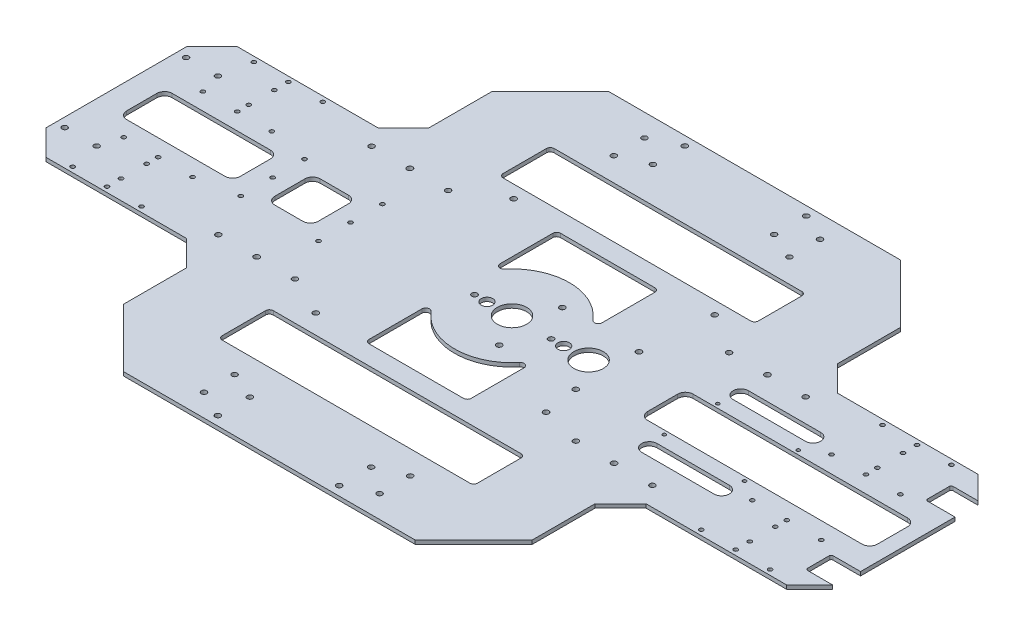
SolidWorks part; units mm, degrees
material "6061-O (SS)"
ref_plane "前视基准面" through (0, 0, 0) normal (0, 0, 1) x (1, 0, 0)
ref_plane "上视基准面" through (0, 0, 0) normal (0, 1, 0) x (1, 0, 0)
ref_plane "右视基准面" through (0, 0, 0) normal (1, 0, 0) x (0, 0, -1)
sketch "草图1" plane through (0, 0, 0) normal (0, 1, 0) x (1, 0, 0)
  line L0 (-310, 75) -> (310, -75) construction
  line L1 (-260, 200) -> (260, 200) construction
  line L2 (-260, 200) -> (-260, -200) construction
  line L3 (-260, -200) -> (260, -200) construction
  line L4 (260, 200) -> (260, -200) construction
  line L5 (310, 75) -> (-310, -75) construction
  line L6 (-160, 200) -> (160, -200) construction
  line L7 (-310, -75) -> (-160, -75)
  line L8 (-310, -75) -> (-310, 75)
  line L9 (-310, 75) -> (-160, 75)
  line L10 (310, -75) -> (310, 75)
  line L11 (160, 200) -> (-160, -200) construction
  line L13 (-160, -200) -> (160, -200)
  line L14 (-160, -200) -> (-160, -75)
  line L15 (-160, 200) -> (160, 200)
  line L16 (160, -200) -> (160, -75)
  line L19 (-160, 75) -> (-160, 200)
  line L22 (160, 75) -> (310, 75)
  line L25 (160, 75) -> (160, 200)
  line L28 (160, -75) -> (310, -75)
  point P0 (0, 0)
  point P6 (-0.5159, 0.1248)
  point P11 (0, 0)
  dimension "D1" = 520
  dimension "D2" = 400
  dimension "D3" = 50
  dimension "D4" = 125
  dimension "D5" = 100
extrude "凸台-拉伸1" add sketch "草图1" along normal blind 3
chamfer "倒角1" distance 20 angle 45 8 edges at (-160, 1.5, -75) (-310, 1.5, -75) (-310, 1.5, 75) (-160, 1.5, 75) (160, 1.5, 75) (160, 1.5, -75) (310, 1.5, 75) (310, 1.5, -75)
sketch "草图2" plane through (0, 3, 0) normal (0, 1, 0) x (1, 0, 0)
  line L0 (-160, 200) -> (-160, 95) construction
  line L1 (-160, 180) -> (160, 180)
  line L2 (-160, 180) -> (-160, 200)
  line L3 (-160, 200) -> (160, 200)
  line L4 (160, 180) -> (160, 200)
  line L6 (160, -200) -> (-160, -200)
  line L7 (160, -200) -> (160, -180)
  line L8 (160, -180) -> (-160, -180)
  line L9 (-160, -200) -> (-160, -180)
  dimension "D1" = 20
  dimension "D2" = 20
extrude "切除-拉伸1" cut sketch "草图2" against normal blind 5
chamfer "倒角2" distance 50 angle 45 4 edges at (-160, 1.5, -180) (-160, 1.5, 180) (160, 1.5, -180) (160, 1.5, 180)
sketch "草图3" plane through (0, 3, 0) normal (0, 1, 0) x (1, 0, 0)
  line L0 (0, 0) -> (144.0598, 0) construction
  line L1 (110, -180) -> (-110, -180) construction
  circle A0 centre (-302.8263, 47.5) radius 2.1
  circle A1 centre (-277.8263, 47.5) radius 2.1
  circle A2 centre (-47.5, 182.8263) radius 2.1
  circle A3 centre (-47.5, 157.8263) radius 2.1
  circle A4 centre (47.5, 182.8263) radius 2.1
  circle A5 centre (47.5, 157.8263) radius 2.1
  circle A6 centre (302.7002, 47.5) radius 2.1
  circle A7 centre (327.7002, 47.5) radius 2.1
  circle A8 centre (-68.75, 172.5) radius 2.1
  circle A9 centre (-68.75, 148.5) radius 2.1
  circle A10 centre (68.75, 172.5) radius 2.1
  circle A11 centre (68.75, 148.5) radius 2.1
  circle A12 centre (68.75, -148.5) radius 2.1
  circle A13 centre (68.75, -172.5) radius 2.1
  circle A14 centre (-68.75, -148.5) radius 2.1
  circle A15 centre (-68.75, -172.5) radius 2.1
  circle A16 centre (327.7002, -47.5) radius 2.1
  circle A17 centre (302.7002, -47.5) radius 2.1
  circle A18 centre (47.5, -157.8263) radius 2.1
  circle A19 centre (47.5, -182.8263) radius 2.1
  circle A20 centre (-47.5, -157.8263) radius 2.1
  circle A21 centre (-47.5, -182.8263) radius 2.1
  circle A22 centre (-277.8263, -47.5) radius 2.1
  circle A23 centre (-302.8263, -47.5) radius 2.1
  dimension "D1" = 4.2
  dimension "D2" = 4.2
  dimension "D3" = 4.2
  dimension "D4" = 4.2
  dimension "D5" = 4.2
  dimension "D6" = 4.2
  dimension "D7" = 4.2
  dimension "D8" = 4.2
  dimension "D9" = 180
extrude "切除-拉伸2" cut sketch "草图3" against normal blind 80
sketch "草图4" plane through (0, 0, 0) normal (0, -1, 0) x (1, 0, 0)
  circle A0 centre (-78.74, 74.91) radius 2.15
  arc A1 (-76.765, 74.91) -> (-80.715, 74.91) centre (-78.74, 74.91) ccw construction
  circle A2 centre (-78.74, -80.01) radius 2.15
  circle A3 centre (78.74, -80.01) radius 2.15
  circle A4 centre (78.74, 52.07) radius 2.15
  dimension "D1" = 4.3
  dimension "D2" = 4.3
  dimension "D3" = 4.3
  dimension "D4" = 4.3
extrude "切除-拉伸3" cut sketch "草图4" against normal blind 10
sketch "草图5" plane through (0, 3, 0) normal (0, 1, 0) x (1, 0, 0)
  line L0 (0, 0) -> (90.3311, 0) construction
  line L1 (0, 0) -> (0, 46.0052) construction
  circle A0 centre (219.2002, 71) radius 1.6
  circle A1 centre (273.2002, 71) radius 1.6
  circle A2 centre (246.2002, 71) radius 1.6
  circle A3 centre (219.2002, 30.9984) radius 1.6
  circle A4 centre (246.2002, 30.9984) radius 1.6
  circle A5 centre (273.2002, 30.9984) radius 1.6
  circle A6 centre (246.2002, 60) radius 1.6
  circle A7 centre (246.2002, 40) radius 1.6
  circle A8 centre (246.2002, -40) radius 1.6
  circle A9 centre (246.2002, -60) radius 1.6
  circle A10 centre (273.2002, -30.9984) radius 1.6
  circle A11 centre (246.2002, -30.9984) radius 1.6
  circle A12 centre (219.2002, -30.9984) radius 1.6
  circle A13 centre (246.2002, -71) radius 1.6
  circle A14 centre (273.2002, -71) radius 1.6
  circle A15 centre (219.2002, -71) radius 1.6
  circle A16 centre (-219.2002, -71) radius 1.6
  circle A17 centre (-273.2002, -71) radius 1.6
  circle A18 centre (-246.2002, -71) radius 1.6
  circle A19 centre (-219.2002, -30.9984) radius 1.6
  circle A20 centre (-246.2002, -30.9984) radius 1.6
  circle A21 centre (-273.2002, -30.9984) radius 1.6
  circle A22 centre (-246.2002, -60) radius 1.6
  circle A23 centre (-246.2002, -40) radius 1.6
  circle A24 centre (-246.2002, 40) radius 1.6
  circle A25 centre (-246.2002, 60) radius 1.6
  circle A26 centre (-273.2002, 30.9984) radius 1.6
  circle A27 centre (-246.2002, 30.9984) radius 1.6
  circle A28 centre (-219.2002, 30.9984) radius 1.6
  circle A29 centre (-246.2002, 71) radius 1.6
  circle A30 centre (-273.2002, 71) radius 1.6
  circle A31 centre (-219.2002, 71) radius 1.6
  circle A32 centre (170, -60) radius 2.1
  circle A34 centre (110, -60) radius 2.1
  circle A35 centre (140, -60) radius 2.2
  circle A36 centre (140, 60) radius 2.2
  circle A37 centre (110, 60) radius 2.1
  circle A38 centre (170, 60) radius 2.1
  circle A39 centre (-170, 60) radius 2.1
  circle A40 centre (-110, 60) radius 2.1
  circle A41 centre (-140, 60) radius 2.2
  circle A42 centre (-140, -60) radius 2.2
  circle A43 centre (-110, -60) radius 2.1
  circle A44 centre (-170, -60) radius 2.1
  dimension "D1" = 3.2
extrude "切除-拉伸4" cut sketch "草图5" against normal blind 29
sketch "草图6" plane through (0, 3, 0) normal (0, 1, 0) x (1, 0, 0)
  line L0 (160, -150) -> (160, -95) construction
  line L1 (0, 0) -> (166.252, 0) construction
  line L2 (-160, 130) -> (-110, 180)
  line L3 (110, 180) -> (-110, 180)
  line L4 (110, 180) -> (160, 130)
  line L5 (-160, -95) -> (-160, -150) construction
  line L12 (160, -144.1421) -> (160, -130)
  line L13 (114.1421, -190) -> (160, -144.1421)
  line L14 (52.4797, -190) -> (114.1421, -190)
  line L15 (-114.1421, -190) -> (-52, -190)
  line L16 (-160, -144.1421) -> (-114.1421, -190)
  line L17 (-160, -130) -> (-160, -144.1421)
  line L25 (-52, -190) -> (52.4797, -190)
  line L28 (110, -180) -> (160, -130) construction
  line L29 (110, -180) -> (-110, -180) construction
  line L30 (-160, -130) -> (-110, -180) construction
  line L31 (110, -180) -> (160, -130)
  line L32 (110, -180) -> (-110, -180)
  line L33 (-160, -130) -> (-110, -180)
  line L37 (-52, 190) -> (52.4797, 190)
  line L38 (-160, 130) -> (-160, 144.1421)
  line L39 (-160, 144.1421) -> (-114.1421, 190)
  line L40 (-114.1421, 190) -> (-52, 190)
  line L41 (52.4797, 190) -> (114.1421, 190)
  line L42 (114.1421, 190) -> (160, 144.1421)
  line L43 (160, 144.1421) -> (160, 130)
  dimension "D1" = 10
  dimension "D2" = 10
  dimension "D3" = 10
extrude "凸台-拉伸2" add sketch "草图6" against normal blind 3 contours L2 | L33 L17 L16 L15 L25 L14 L13 L12 L31 L32 region at (-156.7442, 3, -137.0711) region at (134.7689, 3, 164.7689)
sketch "草图7" plane through (0, 3, 0) normal (0, 1, 0) x (1, 0, 0)
  line L0 (310, -55) -> (310, 55) construction
  line L1 (310, 37) -> (287, 37)
  line L2 (310, 37) -> (310, 57)
  line L3 (310, 57) -> (287, 57)
  line L4 (287, 37) -> (287, 57)
  line L5 (290, 75) -> (180, 75) construction
  line L6 (310, -37) -> (287, -37)
  line L7 (310, -37) -> (310, -57)
  line L8 (310, -57) -> (287, -57)
  line L9 (287, -37) -> (287, -57)
  line L10 (180, -75) -> (290, -75) construction
  dimension "D1" = 18
  dimension "D2" = 20
  dimension "D3" = 20
  dimension "D4" = 18
  dimension "D5" = 23
extrude "切除-拉伸5" cut sketch "草图7" against normal blind 3
fillet "圆角1" radius 1.5 4 edges at (287, 1.5, 37) (287, 1.5, 57) (287, 1.5, -37) (287, 1.5, -57)
sketch "草图9" plane through (0, 0, 0) normal (0, -1, 0) x (1, 0, 0)
  line L0 (-45.449, 182.8784) -> (-49.551, 182.8784) construction
  line L1 (49.551, 182.8784) -> (45.449, 182.8784) construction
  line L2 (0, 0) -> (154.6544, 0) construction
  circle A0 centre (-47.5, 182.8784) radius 2.15
  circle A1 centre (47.5, 182.8784) radius 2.15
  circle A2 centre (47.5, -182.8784) radius 2.15
  circle A3 centre (-47.5, -182.8784) radius 2.15
  dimension "D1" = 4.3
extrude "切除-拉伸6" cut sketch "草图9" against normal blind 3
sketch "草图10" plane through (0, 0, 0) normal (0, -1, 0) x (1, 0, 0)
  circle A0 centre (60, 0) radius 11.5
  circle A1 centre (40.7519, 0.2698) radius 4.5
  circle A2 centre (74.1466, -25.3155) radius 2.15
  circle A3 centre (74.8506, 24.909) radius 2.15
  circle A4 centre (31.0028, 0.4065) radius 2.15
  dimension "D1" = 4.3
  dimension "D2" = 23
  dimension "D3" = 9
extrude "切除-拉伸7" cut sketch "草图10" against normal blind 5
sketch "草图11" plane through (0, 0, 0) normal (0, -1, 0) x (1, 0, 0)
  circle A0 centre (-126.5, -25) radius 1.6 construction
  circle A1 centre (-187.5, -25) radius 1.6 construction
  circle A2 centre (-126.5, 0) radius 1.6 construction
  circle A3 centre (-187.5, 0) radius 1.6 construction
  circle A4 centre (-187.5, 25) radius 1.6 construction
  circle A5 centre (-126.5, 25) radius 1.6 construction
  circle A6 centre (-126.5, -25) radius 1.6
  circle A7 centre (-187.5, -25) radius 1.6
  circle A8 centre (-126.5, 0) radius 1.6
  circle A9 centre (-187.5, 0) radius 1.6
  circle A10 centre (-187.5, 25) radius 1.6
  circle A11 centre (-126.5, 25) radius 1.6
extrude "切除-拉伸8" cut sketch "草图11" against normal blind 10
sketch "草图12" plane through (0, 0, 0) normal (0, -1, 0) x (1, 0, 0)
  circle A0 centre (60, 0) radius 140
  dimension "D1" = 280
sketch "草图13" plane through (0, 3, 0) normal (0, 1, 0) x (1, 0, 0)
  line L0 (143.4002, 35.8) -> (200.0002, 35.8) construction
  line L1 (143.4002, 41.8) -> (200.0002, 41.8)
  line L2 (143.4002, 29.8) -> (200.0002, 29.8)
  line L3 (143.4002, -35.8) -> (200.0002, -35.8) construction
  line L4 (143.4002, -29.8) -> (200.0002, -29.8)
  line L5 (143.4002, -41.8) -> (200.0002, -41.8)
  line L6 (137.4002, 15.5) -> (137.4002, 21) construction
  line L7 (206.0002, -21) -> (206.0002, 21) construction
  line L8 (137.4002, -21) -> (137.4002, -15.5) construction
  line L9 (140.2002, 23.8) -> (203.2002, 23.8) construction
  line L10 (140.2002, -23.8) -> (203.2002, -23.8) construction
  circle A0 centre (140.2002, 21) radius 1.35
  circle A1 centre (203.2002, 21) radius 1.35
  circle A2 centre (203.2002, -21) radius 1.35
  circle A3 centre (140.2002, -21) radius 1.35
  arc A4 (143.4002, 41.8) -> (143.4002, 29.8) centre (143.4002, 35.8) ccw
  arc A5 (200.0002, 29.8) -> (200.0002, 41.8) centre (200.0002, 35.8) ccw
  arc A6 (143.4002, -29.8) -> (143.4002, -41.8) centre (143.4002, -35.8) ccw
  arc A7 (200.0002, -41.8) -> (200.0002, -29.8) centre (200.0002, -35.8) ccw
  point P14 (171.7002, 35.8)
  point P19 (171.7002, -35.8)
  dimension "D3" = 6
  dimension "D6" = 6
  dimension "D1" = 6
  dimension "D2" = 6
  dimension "D4" = 6
  dimension "D5" = 6
  dimension "D7" = 6
  dimension "D8" = 6
extrude "切除-拉伸9" cut sketch "草图13" against normal blind 3
sketch "草图14" plane through (0, 3, 0) normal (0, 1, 0) x (1, 0, 0)
  line L0 (143.4002, 29.8) -> (200.0002, 29.8) construction
  line L1 (292, 17.8) -> (124, 17.8)
  line L2 (298, 11.8) -> (298, -11.8)
  line L3 (292, -17.8) -> (124, -17.8)
  line L4 (118, 11.8) -> (118, -11.8)
  line L5 (200.0002, -29.8) -> (143.4002, -29.8) construction
  line L6 (310, -37) -> (310, 37) construction
  arc A0 (292, 17.8) -> (298, 11.8) centre (292, 11.8) cw
  arc A1 (298, -11.8) -> (292, -17.8) centre (292, -11.8) cw
  arc A2 (124, -17.8) -> (118, -11.8) centre (124, -11.8) cw
  arc A3 (124, 17.8) -> (118, 11.8) centre (124, 11.8) ccw
  point P12 (298, 17.8)
  point P19 (118, 17.8)
  dimension "D5" = 6
  dimension "D1" = 12
  dimension "D2" = 12
  dimension "D3" = 12
  dimension "D4" = 180
extrude "切除-拉伸10" cut sketch "草图14" against normal blind 3
sketch "草图15" plane through (0, 3, 0) normal (0, 1, 0) x (1, 0, 0)
  line L0 (60, 0) -> (-109.9354, 0) construction
  line L1 (74.1466, 25.3155) -> (-47.4576, 25.3155) construction
  line L2 (74.8506, -24.909) -> (-55.7658, -24.909) construction
  line L3 (40.7519, -0.2698) -> (-96.5502, -0.4197) construction
  circle A0 centre (74.8506, -24.909) radius 2.15 construction
  circle A1 centre (74.1466, 25.3155) radius 2.15 construction
  circle A2 centre (31.0028, -0.4065) radius 2.15 construction
  circle A3 centre (40.7519, -0.2698) radius 4.5 construction
  circle A4 centre (60, 0) radius 11.5 construction
  circle A5 centre (74.8506, -24.909) radius 2.15
  circle A6 centre (74.1466, 25.3155) radius 2.15
  circle A7 centre (31.0028, -0.4065) radius 2.15
  circle A8 centre (40.7519, -0.2698) radius 4.5
  circle A9 centre (60, 0) radius 11.5
  circle A10 centre (14.8506, -24.909) radius 2.15
  circle A11 centre (14.1466, 25.3155) radius 2.15
  circle A12 centre (-28.9972, -0.3459) radius 2.15
  circle A13 centre (-19.2481, -0.3353) radius 4.5
  circle A14 centre (0, 0) radius 11.5
  dimension "D1" = 60
  dimension "D2" = 60
  dimension "D3" = 60
  dimension "D4" = 60
  dimension "D5" = 60
extrude "切除-拉伸11" cut sketch "草图15" against normal blind 3
sketch "草图16" plane through (0, 3, 0) normal (0, 1, 0) x (1, 0, 0)
  line L2 (-114.1421, 190) -> (114.1421, 190) construction
  line L7 (-97, 130) -> (97, 130)
  line L8 (-100, 127) -> (-100, 93)
  line L44 (-97, 90) -> (-40, 90)
  line L45 (-40, -90) -> (40, -90)
  line L53 (100, 127) -> (100, 93)
  line L70 (-40, 130) -> (40, 130)
  line L71 (-40, 72) -> (-40, 30.5778)
  line L72 (-40, -130) -> (40, -130)
  line L73 (40, 72) -> (40, 30.5778)
  line L74 (-97, -90) -> (-40, -90)
  line L75 (-100, -93) -> (-100, -127)
  line L76 (-97, -130) -> (97, -130)
  line L77 (100, -93) -> (100, -127)
  line L78 (-114.1421, -190) -> (114.1421, -190) construction
  line L79 (160, 95) -> (160, 144.1421) construction
  line L80 (-160, 144.1421) -> (-160, 95) construction
  line L81 (40, 90) -> (97, 90)
  line L82 (-40, -30.5778) -> (-40, -72)
  line L83 (40, -30.5778) -> (40, -72)
  line L84 (40, -90) -> (97, -90)
  line L85 (-37, -75) -> (37, -75)
  line L87 (-40, 90) -> (40, 90)
  line L89 (-37, 75) -> (37, 75)
  arc A56 (-34.6875, -28.6667) -> (34.6875, -28.6667) centre (0, 0) ccw
  arc A57 (34.6875, 28.6667) -> (-34.6875, 28.6667) centre (0, 0) ccw
  arc A58 (-40, -72) -> (-37, -75) centre (-37, -72) ccw
  arc A59 (37, -75) -> (40, -72) centre (37, -72) ccw
  arc A60 (97, -130) -> (100, -127) centre (97, -127) ccw
  arc A61 (97, -90) -> (100, -93) centre (97, -93) cw
  arc A62 (-100, -127) -> (-97, -130) centre (-97, -127) ccw
  arc A63 (-97, -90) -> (-100, -93) centre (-97, -93) ccw
  arc A64 (-100, 93) -> (-97, 90) centre (-97, 93) ccw
  arc A65 (-97, 130) -> (-100, 127) centre (-97, 127) ccw
  arc A66 (97, 130) -> (100, 127) centre (97, 127) cw
  arc A67 (97, 90) -> (100, 93) centre (97, 93) ccw
  arc A68 (37, 75) -> (40, 72) centre (37, 72) cw
  arc A69 (-40, 72) -> (-37, 75) centre (-37, 72) cw
  arc A70 (-34.6875, -28.6667) -> (-40, -30.5778) centre (-37, -30.5778) ccw
  arc A71 (40, -30.5778) -> (34.6875, -28.6667) centre (37, -30.5778) ccw
  arc A72 (40, 30.5778) -> (34.6875, 28.6667) centre (37, 30.5778) cw
  arc A73 (-34.6875, 28.6667) -> (-40, 30.5778) centre (-37, 30.5778) cw
  point P39 (100, -130)
  point P42 (100, -90)
  point P53 (100, 130)
  point P56 (100, 90)
  point P63 (-40, -20.6155)
  point P68 (40, 20.6155)
  dimension "D5" = 60
  dimension "D11" = 90
  dimension "D14" = 3
  dimension "D1" = 60
  dimension "D2" = 60
  dimension "D3" = 60
  dimension "D4" = 60
  dimension "D6" = 60
  dimension "D7" = 60
  dimension "D8" = 60
  dimension "D9" = 40
  dimension "D10" = 40
  dimension "D12" = 15
  dimension "D13" = 15
extrude "切除-拉伸12" cut sketch "草图16" against normal blind 3 contours L81 A67 L53 A66 L7 A65 L8 A64 L44 L87 | A73 A57 A72 L73 A68 L89 A69 L71 | L83 A71 A56 A70 L82 A58 L85 A59 | L74 A63 L75 A62 L76 L72 A60 L77 A61 L84 L45 region at (0, 3, -110) region at (0, 3, 110) region at (0, 3, -56.2095) region at (0, 3, 56.2095)
sketch "草图17" plane through (0, 3, 0) normal (0, 1, 0) x (1, 0, 0)
  line L1 (-283.954, 17.8) -> (-207, 17.8)
  line L2 (-289.954, 11.8) -> (-289.954, -11.8)
  line L3 (-283.954, -17.8) -> (-207, -17.8)
  line L4 (-201, 11.8) -> (-201, -11.8)
  line L5 (-168, 17.8) -> (-146, 17.8)
  line L6 (-174, 11.8) -> (-174, -11.8)
  line L7 (-168, -17.8) -> (-146, -17.8)
  line L8 (-140, 11.8) -> (-140, -11.8)
  line L14 (-301.954, 33.3431) -> (-301.954, -33.3431) construction
  line L15 (-195, -30) -> (-195, 30) construction
  line L16 (-180, -45) -> (-180, 45) construction
  line L17 (-134, -30) -> (-134, 30) construction
  arc A4 (-146, 17.8) -> (-140, 11.8) centre (-146, 11.8) cw
  arc A5 (-146, -17.8) -> (-140, -11.8) centre (-146, -11.8) ccw
  arc A6 (-174, -11.8) -> (-168, -17.8) centre (-168, -11.8) ccw
  arc A7 (-168, 17.8) -> (-174, 11.8) centre (-168, 11.8) ccw
  arc A8 (-207, 17.8) -> (-201, 11.8) centre (-207, 11.8) cw
  arc A9 (-207, -17.8) -> (-201, -11.8) centre (-207, -11.8) ccw
  arc A10 (-289.954, -11.8) -> (-283.954, -17.8) centre (-283.954, -11.8) ccw
  arc A11 (-283.954, 17.8) -> (-289.954, 11.8) centre (-283.954, 11.8) ccw
  dimension "D1" = 12
  dimension "D2" = 6
  dimension "D3" = 6
  dimension "D4" = 6
extrude "切除-拉伸13" cut sketch "草图17" against normal blind 3
